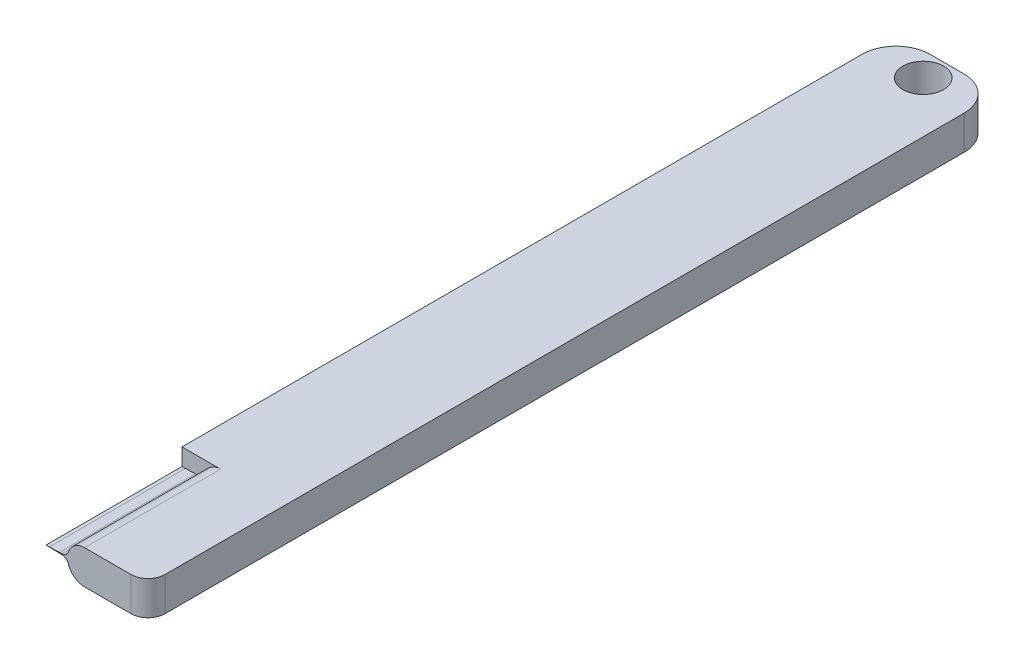
SolidWorks part; units mm, degrees
ref_plane "Front Plane" through (0, 0, 0) normal (0, 0, 1) x (1, 0, 0)
ref_plane "Top Plane" through (0, 0, 0) normal (0, 1, 0) x (1, 0, 0)
ref_plane "Right Plane" through (0, 0, 0) normal (1, 0, 0) x (0, 0, -1)
sketch "Sketch2" plane through (0, 0, 0) normal (0, 0, 1) x (1, 0, 0)
  line L1 (0, 0) -> (30, 0)
  line L2 (0, 0) -> (0, 10)
  line L3 (0, 10) -> (30, 10)
  line L4 (30, 0) -> (30, 10)
  dimension "D1" = 10
  dimension "D2" = 30
extrude "Boss-Extrude1" add sketch "Sketch2" along normal blind 250
sketch "Sketch3" plane through (0, 10, 0) normal (0, 1, 0) x (1, 0, 0)
  line L0 (30, 0) -> (0, 0) construction
  circle A0 centre (15, -7) radius 6
  point P2 (15, 0)
  dimension "D1" = 12
  dimension "D2" = 7
extrude "Cut-Extrude1" cut sketch "Sketch3" against normal blind 30
fillet "Fillet1" radius 10 1 edges at (30, 5, 0)
fillet "Fillet3" radius 10 1 edges at (0, 5, 0)
sketch "Sketch5" plane through (0, 0, 250) normal (0, 0, 1) x (1, 0, 0)
  line L0 (0, 5) -> (1, 5.0175)
  line L1 (0, 10) -> (0, 0) construction
  line L2 (1, 5.0175) -> (4, 5.1222)
  line L3 (4, 5.1222) -> (4.6874, 5.1342)
  line L4 (6.5011, 6.3705) -> (8, 10)
  line L5 (30, 10) -> (0, 10) construction
  line L6 (8, 10) -> (0, 10)
  line L7 (0, 10) -> (0, 0)
  line L8 (0, 5) -> (3.4589, 5) construction
  line L9 (8, 0) -> (0, 0)
  line L10 (6.5011, 3.6295) -> (8, 0)
  line L11 (4, 4.8778) -> (4.6874, 4.8658)
  line L12 (1, 4.9825) -> (4, 4.8778)
  line L13 (0, 5) -> (1, 4.9825)
  arc A0 (6.5011, 6.3705) -> (4.6874, 5.1342) centre (4.6525, 7.1339) cw
  arc A1 (4.6874, 4.8658) -> (6.5011, 3.6295) centre (4.6525, 2.8661) cw
  point P19 (6, 5.1571)
  point P22 (6, 4.8429)
  line M2 (0, 10) -> (0, 0)
  line M3 (0, 0) -> (30, 0)
  line M5 (30, 10) -> (0, 10)
  dimension "D7" = 2
  dimension "D8" = 2
  dimension "D1" = 1
  dimension "D2" = 3
  dimension "D3" = 2
  dimension "D4" = 2
  dimension "D5" = 2
  dimension "D6" = 1
extrude "Cut-Extrude2" cut sketch "Sketch5" against normal blind 40 contours L3 L4 L0 L2 M5 M2 | L13 L10 L11 L12 M2 M3 region at (3.4811, 7.6803, 250) region at (3.4811, 2.3197, 250)
fillet "Fillet4" radius 5 1 edges at (8, 10, 230)
fillet "Fillet5" radius 5 1 edges at (8, 0, 230)
fillet "Fillet6" radius 5 1 edges at (30, 5, 250)
